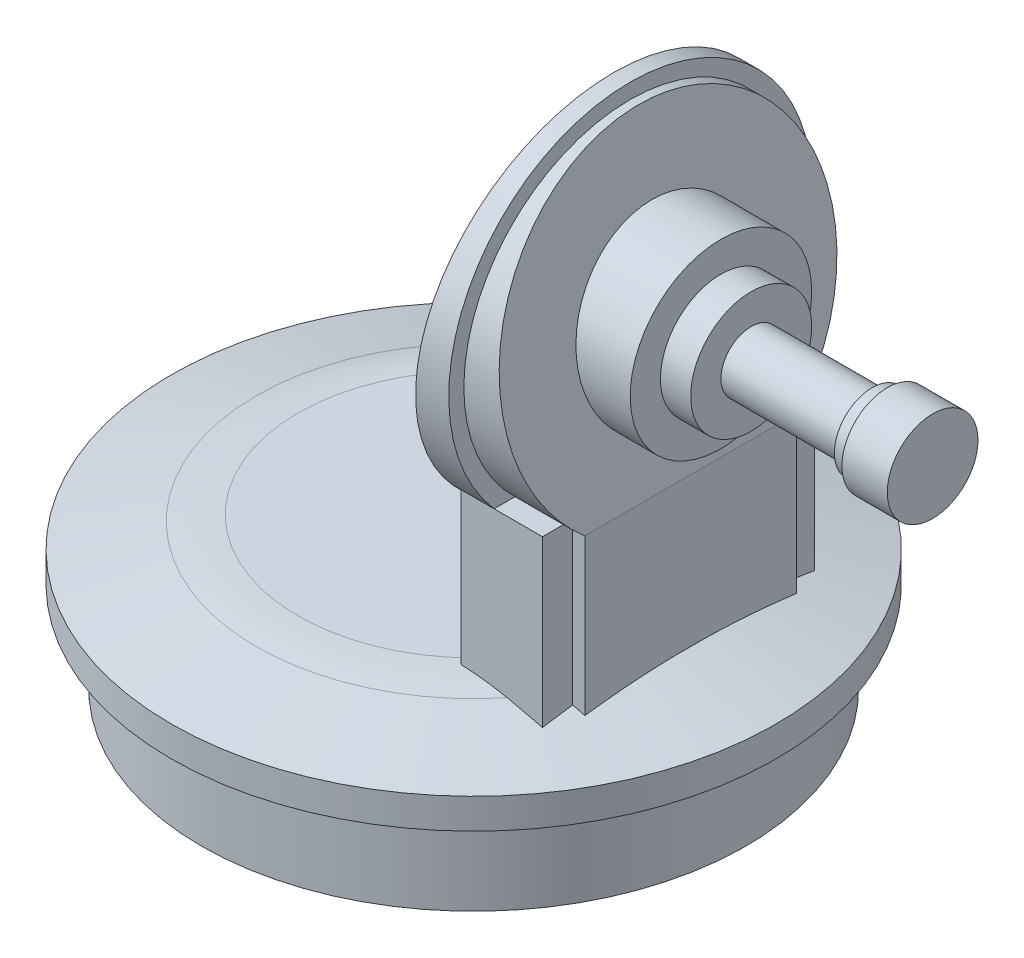
SolidWorks part; units mm, degrees
material "Ti-6Al-2Sn-2Zr-2Mo-2Cr-0.25Si (SS)"
ref_plane "Front Plane" through (0, 0, 0) normal (0, 0, 1) x (1, 0, 0)
ref_plane "Top Plane" through (0, 0, 0) normal (0, 1, 0) x (1, 0, 0)
ref_plane "Right Plane" through (0, 0, 0) normal (1, 0, 0) x (0, 0, -1)
sketch "Sketch2" plane through (0, 0, 0) normal (0, 1, 0) x (1, 0, 0)
  circle A0 centre (0, 0) radius 90
  dimension "D1" = 180
extrude "Boss-Extrude1" add sketch "Sketch2" along normal blind 30
sketch "Sketch3" plane through (0, 30, 0) normal (0, 1, 0) x (1, 0, 0)
  circle A0 centre (0, 0) radius 100
  dimension "D1" = 200
extrude "Boss-Extrude2" add sketch "Sketch3" along normal blind 20
chamfer "Chamfer1" distance 10 angle 74 1 edges at (0, 50, 100) first distance on face at (0, 50, 100)
fillet "Fillet1" radius 50 1 edges at (0, 50, 65.1259)
sketch "Sketch5" plane through (0, 50, 0) normal (0, 1, 0) x (1, 0, 0)
  line L0 (54.2488, 0) -> (36.7488, 0) construction
  line L1 (71.7488, -45) -> (36.7488, -45)
  line L2 (71.7488, -45) -> (71.7488, 45)
  line L3 (71.7488, 45) -> (36.7488, 45)
  line L4 (36.7488, -45) -> (36.7488, 45)
  line L5 (71.7488, -45) -> (36.7488, 45) construction
  line L6 (71.7488, 45) -> (36.7488, -45) construction
  line L7 (36.7488, 45) -> (40.7488, 45)
  line L8 (36.7488, 45) -> (36.7488, 35)
  line L9 (36.7488, 35) -> (40.7488, 35)
  line L10 (40.7488, 45) -> (40.7488, 35)
  line L11 (71.7488, 45) -> (67.7488, 45)
  line L12 (71.7488, 45) -> (71.7488, 35)
  line L13 (71.7488, 35) -> (67.7488, 35)
  line L14 (67.7488, 45) -> (67.7488, 35)
  line L15 (71.7488, -35) -> (67.7488, -35)
  line L16 (67.7488, -45) -> (67.7488, -35)
  line L17 (36.7488, -35) -> (40.7488, -35)
  line L18 (40.7488, -45) -> (40.7488, -35)
  circle A2 centre (0, 0) radius 58.0988 construction
  point P0 (54.2488, 0)
  dimension "D1" = 90
  dimension "D2" = 35
  dimension "D3" = 10
  dimension "D4" = 4
extrude "Boss-Extrude4" add sketch "Sketch5" along normal blind 50 and the other way blind 5 contours L18 L9 L10 L4 L17 | L18 L1 L16 L15 L2 L13 L14 L3 L10 L9 region at (54.2488, 50, 0)
ref_plane "Plane1" through (51.7488, 0, 0) normal (-1, 0, 0) x (0, 0, 1)
sketch "Sketch6" plane through (51.7488, 0, 0) normal (-1, 0, 0) x (0, 0, 1)
  line L1 (-45, 49.9319) -> (-45, 100) construction
  circle A0 centre (0, 139.6863) radius 60
  dimension "D3" = 120
  dimension "D2" = 45
extrude "Boss-Extrude5" add sketch "Sketch6" along normal blind 15
sketch "Sketch7" plane through (51.7488, 0, 0) normal (1, 0, 0) x (0, 0, -1)
  circle A0 centre (0, 139.6863) radius 55
  circle A1 centre (0, 139.6863) radius 30
  dimension "D1" = 110
  dimension "D2" = 60
extrude "Boss-Extrude7" add sketch "Sketch7" along normal blind 20
sketch "Sketch8" plane through (36.7488, 0, 0) normal (-1, 0, 0) x (0, 0, 1)
  line L0 (-35, 90.9523) -> (35, 90.9523) construction
ref_plane "Plane2" through (28.5728, -2.4998, 0) normal (0.9962, -0.0872, 0) x (0, 0, 1)
sketch "Sketch9" plane through (28.5728, -2.4998, 0) normal (0.9962, -0.0872, 0) x (0, 0, 1)
  line L1 (69.1337, -83.1747) -> (-74.2585, -83.1747)
  line L2 (69.1337, -83.1747) -> (69.1337, -214.4445)
  line L3 (69.1337, -214.4445) -> (-74.2585, -214.4445)
  line L4 (-74.2585, -83.1747) -> (-74.2585, -214.4445)
extrude "Cut-Extrude1" cut sketch "Sketch9" against normal blind 20
sketch "Sketch10" plane through (71.7488, 0, 0) normal (1, 0, 0) x (0, 0, -1)
  line L0 (-35, 97.2599) -> (35, 97.2599) construction
ref_plane "Plane3" through (86.2177, 15.2025, 0) normal (-0.9848, -0.1736, 0) x (0, 0, -1)
sketch "Sketch11" plane through (86.2177, 15.2025, 0) normal (-0.9848, -0.1736, 0) x (0, 0, -1)
  line L1 (64.3683, -71.7281) -> (-74.7712, -71.7281)
  line L2 (64.3683, -71.7281) -> (64.3683, -191.6871)
  line L3 (64.3683, -191.6871) -> (-74.7712, -191.6871)
  line L4 (-74.7712, -71.7281) -> (-74.7712, -191.6871)
extrude "Cut-Extrude2" cut sketch "Sketch11" against normal blind 20
extrude "Boss-Extrude9" add sketch "Sketch7<4>" along normal blind 30 contours A1 region at (51.7488, 139.6863, 0)
sketch "Sketch7<4>" plane through (51.7488, 0, 0) normal (1, 0, 0) x (0, 0, -1) same geometry as "Sketch7"
sketch "Sketch12" plane through (81.7488, 0, 0) normal (1, 0, 0) x (0, 0, -1)
  circle A0 centre (0, 139.6863) radius 20
  dimension "D1" = 40
extrude "Boss-Extrude10" add sketch "Sketch12" along normal blind 10
sketch "Sketch13" plane through (91.7488, 0, 0) normal (1, 0, 0) x (0, 0, -1)
  circle A0 centre (0, 139.6863) radius 10
  dimension "D1" = 20
extrude "Boss-Extrude11" add sketch "Sketch13" along normal blind 40
sketch "Sketch14" plane through (131.7488, 0, 0) normal (1, 0, 0) x (0, 0, -1)
  circle A0 centre (0, 139.6863) radius 12.5
  dimension "D1" = 25
extrude "Boss-Extrude12" add sketch "Sketch14" along normal blind 5
extrude "Cut-Extrude3" cut sketch "Sketch7<5>" against normal blind 15 contours A1 region at (51.7488, 139.6863, 0)
sketch "Sketch7<5>" plane through (51.7488, 0, 0) normal (1, 0, 0) x (0, 0, -1) same geometry as "Sketch7"
sketch "Sketch16" plane through (136.7488, 0, 0) normal (1, 0, 0) x (0, 0, -1)
  circle A0 centre (0, 139.6863) radius 15
  dimension "D1" = 30
extrude "Boss-Extrude13" add sketch "Sketch16" along normal blind 15
scale "Scale1" scale about centroid uniform scaling yes scale factor 0.3
